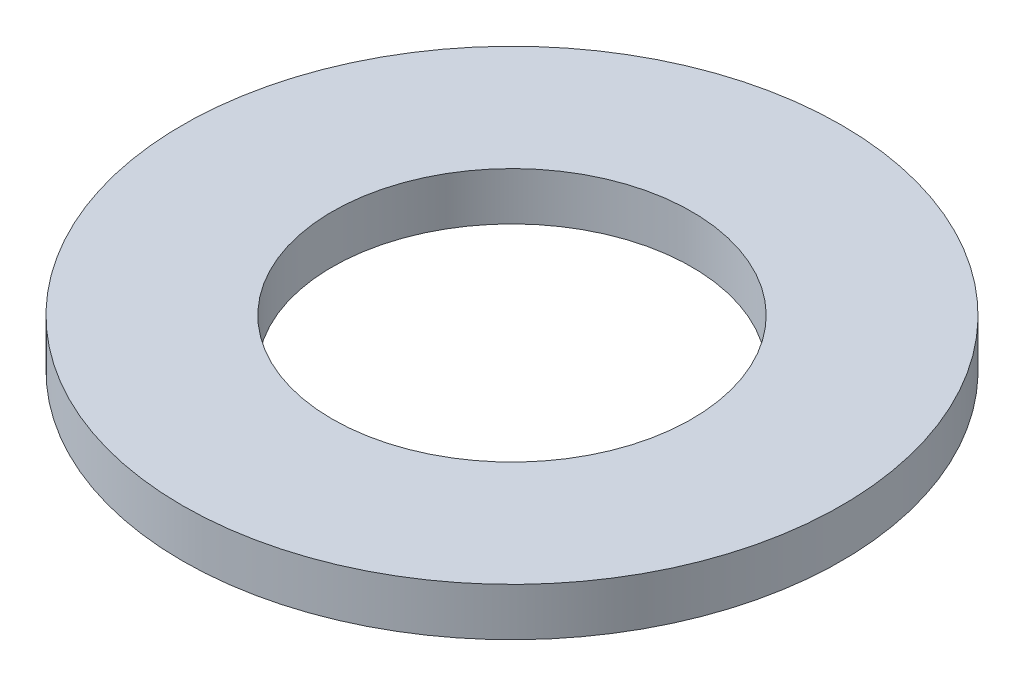
SolidWorks part; units mm, degrees
ref_plane "Front Plane" through (0, 0, 0) normal (0, 0, 1) x (1, 0, 0)
ref_plane "Top Plane" through (0, 0, 0) normal (0, 1, 0) x (1, 0, 0)
ref_plane "Right Plane" through (0, 0, 0) normal (1, 0, 0) x (0, 0, -1)
sketch "Sketch1" plane through (0, 0, 0) normal (0, 1, 0) x (1, 0, 0)
  circle A0 centre (0, 0) radius 55
  dimension "FLANGE_OD" = 110
extrude "Boss-Extrude1" add sketch "Sketch1" along normal blind 8
sketch "Sketch2" plane through (0, 0, 0) normal (0, 1, 0) x (1, 0, 0)
  circle A0 centre (0, 0) radius 30
  dimension "BORE_D" = 60
extrude "Cut-Extrude1" cut sketch "Sketch2" along normal through all
sketch "Sketch3" plane through (0, 8, 0) normal (0, 1, 0) x (1, 0, 0)
  circle A0 centre (0, 0) radius 20.9995 construction
  circle A1 centre (-20.9995, 0) radius 2.0953
  dimension "BOLT_D" = 4.1905
  dimension "BOLT_PCD" = 41.9991
extrude "Cut-Extrude2" cut sketch "Sketch3" against normal blind 6.5253 rebuild error yes
pattern_circular "CirPattern1" count 4 over 360 rebuild error yes
